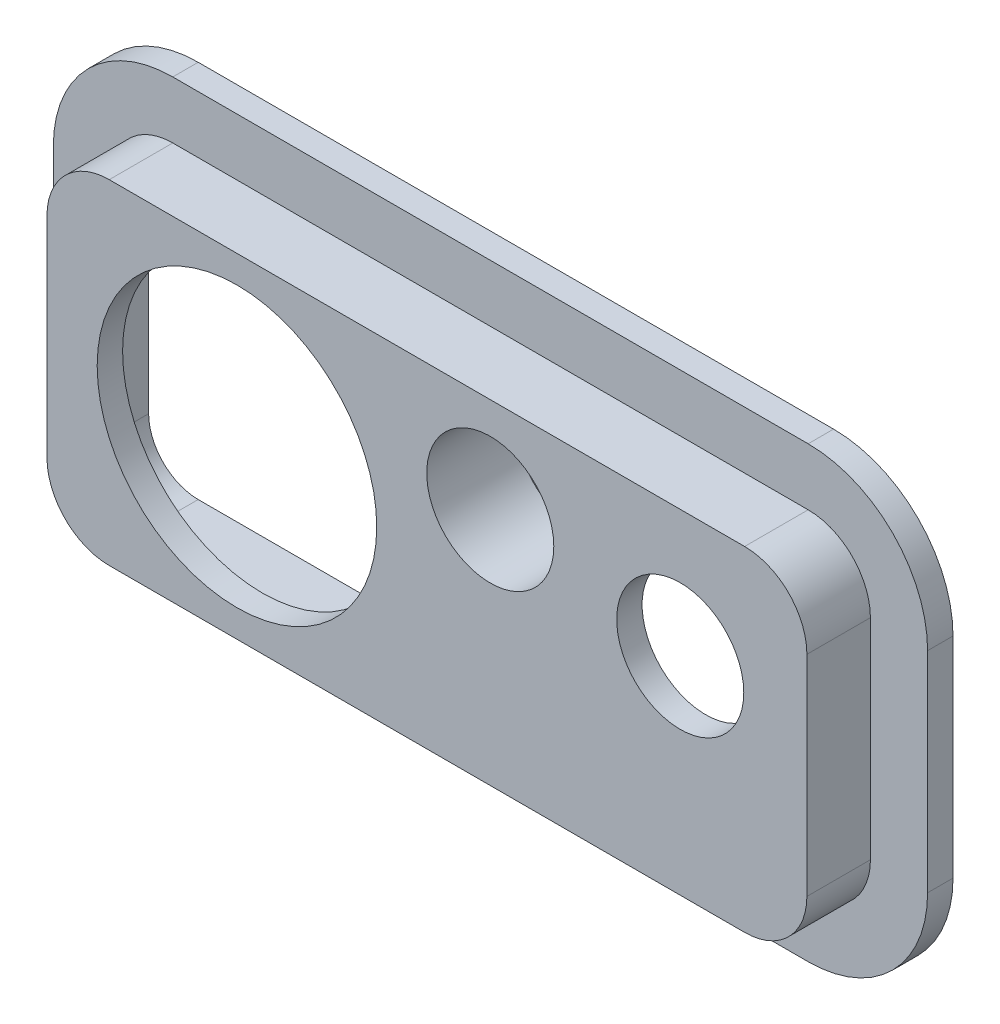
SolidWorks part; units mm, degrees
ref_plane "Front Plane" through (0, 0, 0) normal (0, 0, 1) x (1, 0, 0)
ref_plane "Top Plane" through (0, 0, 0) normal (0, 1, 0) x (1, 0, 0)
ref_plane "Right Plane" through (0, 0, 0) normal (1, 0, 0) x (0, 0, -1)
sketch "Sketch1" plane through (0, 0, 0) normal (0, 0, 1) x (1, 0, 0)
  line L26 (-29.9, 17.1) -> (-29.9, 0.6)
  line L27 (25, 22) -> (-25, 22)
  line L28 (29.9, 0.6) -> (29.9, 17.1)
  line L29 (-25, -4.3) -> (25, -4.3)
  line L30 (-29.9, 17.1) -> (-29.9, 0.6)
  line L31 (25, 22) -> (-25, 22)
  line L32 (29.9, 0.6) -> (29.9, 17.1)
  line L33 (-25, -4.3) -> (25, -4.3)
  arc A18 (-29.9, 0.6) -> (-25, -4.3) centre (-25, 0.6) ccw
  arc A19 (-25, 22) -> (-29.9, 17.1) centre (-25, 17.1) ccw
  arc A20 (29.9, 17.1) -> (25, 22) centre (25, 17.1) ccw
  arc A21 (25, -4.3) -> (29.9, 0.6) centre (25, 0.6) ccw
  arc A22 (-29.9, 0.6) -> (-25, -4.3) centre (-25, 0.6) ccw
  arc A23 (-25, 22) -> (-29.9, 17.1) centre (-25, 17.1) ccw
  arc A24 (29.9, 17.1) -> (25, 22) centre (25, 17.1) ccw
  arc A25 (25, -4.3) -> (29.9, 0.6) centre (25, 0.6) ccw
  dimension "D1" = 0.1
extrude "Boss-Extrude1" add sketch "Sketch1" against normal blind 5
sketch "Sketch2" plane through (0, 0, -5) normal (0, 0, -1) x (-1, 0, 0)
  line L4 (34.4, 0.6) -> (34.4, 17.1)
  line L5 (25, 26.5) -> (-25, 26.5)
  line L6 (-34.4, 17.1) -> (-34.4, 0.6)
  line L7 (-25, -8.8) -> (25, -8.8)
  line L8 (28.9, 0.6) -> (28.9, 17.1)
  line L9 (25, 21) -> (-25, 21)
  line L10 (-28.9, 17.1) -> (-28.9, 0.6)
  line L11 (-25, -3.3) -> (25, -3.3)
  line L12 (28.9, 0.6) -> (28.9, 17.1)
  line L13 (25, 21) -> (-25, 21)
  line L14 (-28.9, 17.1) -> (-28.9, 0.6)
  line L15 (-25, -3.3) -> (25, -3.3)
  arc A4 (25, -8.8) -> (34.4, 0.6) centre (25, 0.6) ccw
  arc A5 (34.4, 17.1) -> (25, 26.5) centre (25, 17.1) ccw
  arc A6 (-25, 26.5) -> (-34.4, 17.1) centre (-25, 17.1) ccw
  arc A7 (-34.4, 0.6) -> (-25, -8.8) centre (-25, 0.6) ccw
  arc A8 (25, -3.3) -> (28.9, 0.6) centre (25, 0.6) ccw
  arc A9 (28.9, 17.1) -> (25, 21) centre (25, 17.1) ccw
  arc A10 (-25, 21) -> (-28.9, 17.1) centre (-25, 17.1) ccw
  arc A11 (-28.9, 0.6) -> (-25, -3.3) centre (-25, 0.6) ccw
  arc A12 (25, -3.3) -> (28.9, 0.6) centre (25, 0.6) ccw
  arc A13 (28.9, 17.1) -> (25, 21) centre (25, 17.1) ccw
  arc A14 (-25, 21) -> (-28.9, 17.1) centre (-25, 17.1) ccw
  arc A15 (-28.9, 0.6) -> (-25, -3.3) centre (-25, 0.6) ccw
  dimension "D1" = 1
  dimension "D2" = 5.5
extrude "Boss-Extrude3" add sketch "Sketch2" along normal blind 2
sketch "Sketch3" plane through (0, 0, -5) normal (0, 0, -1) x (-1, 0, 0)
  line L0 (-25, -3.3) -> (25, -3.3) construction
  line L1 (28.9, 0.6) -> (28.9, 17.1) construction
  line L2 (25, 21) -> (-25, 21) construction
  line L3 (-28.9, 17.1) -> (-28.9, 0.6) construction
  line L4 (-25, -3.3) -> (25, -3.3)
  line L5 (28.9, 0.6) -> (28.9, 17.1)
  line L6 (25, 21) -> (-25, 21)
  line L7 (-28.9, 17.1) -> (-28.9, 0.6)
  arc A0 (-28.9, 0.6) -> (-25, -3.3) centre (-25, 0.6) ccw construction
  arc A1 (25, -3.3) -> (28.9, 0.6) centre (25, 0.6) ccw construction
  arc A2 (28.9, 17.1) -> (25, 21) centre (25, 17.1) ccw construction
  arc A3 (-25, 21) -> (-28.9, 17.1) centre (-25, 17.1) ccw construction
  arc A4 (-28.9, 0.6) -> (-25, -3.3) centre (-25, 0.6) ccw
  arc A5 (25, -3.3) -> (28.9, 0.6) centre (25, 0.6) ccw
  arc A6 (28.9, 17.1) -> (25, 21) centre (25, 17.1) ccw
  arc A7 (-25, 21) -> (-28.9, 17.1) centre (-25, 17.1) ccw
extrude "Cut-Extrude1" cut sketch "Sketch3" against normal offset from surface (3 mm away) 2 up to face at (0, 8.85, 0)
sketch "Sketch4" plane through (0, 0, 0) normal (0, 0, 1) x (1, 0, 0)
  line L0 (-29.9, 8.85) -> (-14.95, 8.85) construction
  line L2 (-29.9, 17.1) -> (-29.9, 0.6) construction
  line L3 (-14.95, 8.85) -> (0, 8.85) construction
  line L4 (0, 8.85) -> (9.9667, 8.85) construction
  line L5 (9.9667, 8.85) -> (19.9333, 8.85) construction
  line L6 (19.9333, 8.85) -> (29.9, 8.85) construction
  line L8 (29.9, 0.6) -> (29.9, 17.1) construction
  line L9 (25, 22) -> (-25, 22) construction
  line L10 (19.9333, 17) -> (19.9333, 22) construction
  circle A0 centre (4.9833, 14.5) radius 5
  circle A1 centre (-14.95, 8.85) radius 11
  circle A2 centre (19.9333, 12) radius 5
  point P15 (-29.9, 8.85)
  point P18 (4.9833, 8.85)
  dimension "D1" = 10
  dimension "D2" = 22
  dimension "D4" = 5
  dimension "D3" = 7.5
extrude "Cut-Extrude2" cut sketch "Sketch4" against normal through all
sketch "Sketch5" plane through (0, 0, -2) normal (0, 0, -1) x (-1, 0, 0)
  circle A1 centre (-4.9833, 14.5) radius 5 construction
  circle A2 centre (-4.9833, 14.5) radius 7
  circle A3 centre (-4.9833, 14.5) radius 7
  circle A4 centre (-4.9833, 14.5) radius 5
  dimension "D1" = 2
extrude "Boss-Extrude4" add sketch "Sketch5" along normal blind 5
fillet "Fillet1" radius 1 1 edges at (4.9833, 7.5, -2) second distance 3 first distance on face at (-3.95, 8.85, -2)
